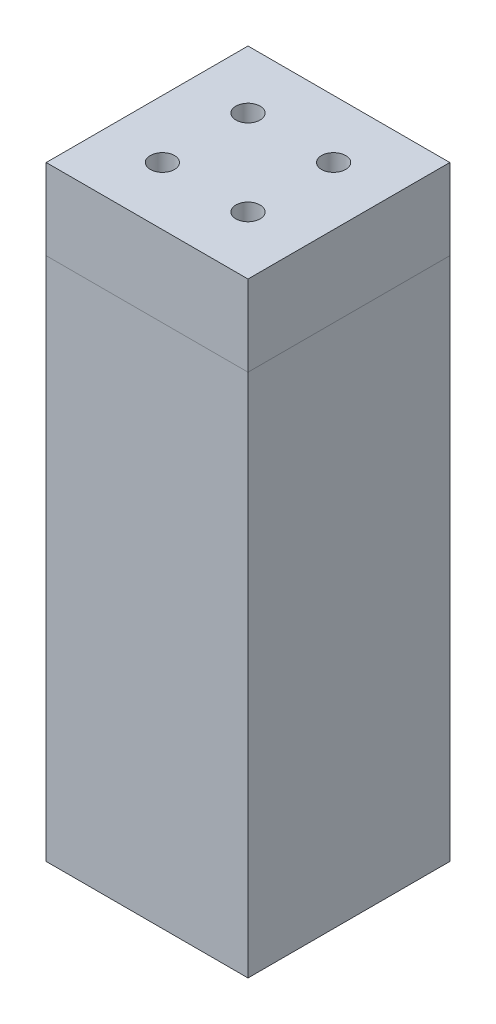
SolidWorks part; units mm, degrees
material "Plain Carbon Steel"
ref_plane "Front Plane" through (0, 0, 0) normal (0, 0, 1) x (1, 0, 0)
ref_plane "Top Plane" through (0, 0, 0) normal (0, 1, 0) x (1, 0, 0)
ref_plane "Right Plane" through (0, 0, 0) normal (1, 0, 0) x (0, 0, -1)
sketch "Sketch1" plane through (0, 0, 0) normal (0, 1, 0) x (1, 0, 0)
  line L1 (12.5, 12.5) -> (-12.5, 12.5)
  line L2 (12.5, 12.5) -> (12.5, -12.5)
  line L3 (12.5, -12.5) -> (-12.5, -12.5)
  line L4 (-12.5, 12.5) -> (-12.5, -12.5)
  line L5 (0, -12.5) -> (0, 12.5) construction
  line L6 (12.5, 0) -> (-12.5, 0) construction
  point P0 (0, 0)
  dimension "D1" = 25
  dimension "D2" = 25
extrude "Boss-Extrude1" add sketch "Sketch1" along normal blind 75
hole_wizard "M3x0.5 Tapped Hole1" positions "Sketch3" profile "Sketch2" tap size "M3x0.5" standard "ANSI Metric"
sketch "Sketch3" plane through (0, 75, 0) normal (0, 1, 0) x (1, 0, 0)
  line L0 (-5.3033, 5.3033) -> (5.3033, -5.3033) construction
  line L3 (5.3033, 5.3033) -> (-5.3033, -5.3033) construction
  line L4 (0, 0) -> (0, -5.4471) construction
  point P0 (-5.3033, -5.3033)
  point P2 (5.3033, -5.3033)
  point P4 (5.3033, 5.3033)
  point P6 (-5.3033, 5.3033)
  dimension "D1" = 15
  dimension "D2" = 45
sketch "Sketch2" plane through (-5.3033, 75, 5.3033) normal (1, 0, 0) x (0, 0, 1)
  line L0 (0, 0) -> (0, 35.9013)
  line L1 (0, 35.9013) -> (1.5, 35)
  line L2 (1.5, 35) -> (1.5, 0)
  line L5 (1.5, 0) -> (0, 0)
  line L10 (0, 35.9013) -> (-1.5, 35) construction
  line L11 (0, -6.35) -> (0, 107.95) construction
  dimension "Tap Drill Dia." = 3
  dimension "Tap Drill Depth" = 35
  dimension "Drill Angle" = 118
cosmetic thread "Hole Thread1" parameters "D1"=6, "D2"=3
cosmetic thread "Hole Thread2" parameters "D1"=6, "D2"=3
cosmetic thread "Hole Thread3" parameters "D1"=6, "D2"=3
cosmetic thread "Hole Thread4" parameters "D1"=6, "D2"=3
sketch "Sketch4" plane through (0, 0, 12.5) normal (0, 0, 1) x (1, 0, 0)
  line L0 (-12.5, 75) -> (-12.5, 0) construction
  line L1 (-12.5, 65) -> (12.5, 65)
  line L5 (-36.3173, 75) -> (36.3173, 75) construction
  dimension "D1" = 10
split line "Split Line1"
